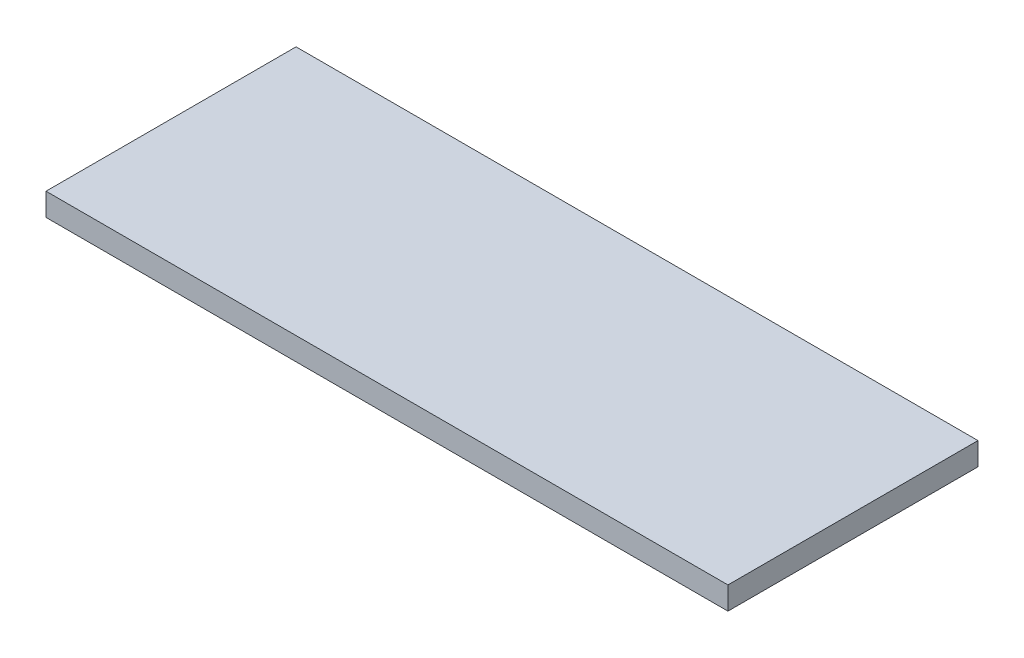
SolidWorks part; units mm, degrees
ref_plane "Front Plane" through (0, 0, 0) normal (0, 0, 1) x (1, 0, 0)
ref_plane "Top Plane" through (0, 0, 0) normal (0, 1, 0) x (1, 0, 0)
ref_plane "Right Plane" through (0, 0, 0) normal (1, 0, 0) x (0, 0, -1)
sketch "Sketch1" plane through (0, 0, 0) normal (0, 1, 0) x (1, 0, 0)
  line L1 (-47.625, -17.4625) -> (47.625, -17.4625)
  line L2 (-47.625, -17.4625) -> (-47.625, 17.4625)
  line L3 (-47.625, 17.4625) -> (47.625, 17.4625)
  line L4 (47.625, -17.4625) -> (47.625, 17.4625)
  line L5 (-47.625, -17.4625) -> (47.625, 17.4625) construction
  line L6 (-47.625, 17.4625) -> (47.625, -17.4625) construction
  point P0 (0, 0)
  dimension "D1" = 95.25
  dimension "D2" = 34.925
extrude "Boss-Extrude1" add sketch "Sketch1" along normal blind 3.175
